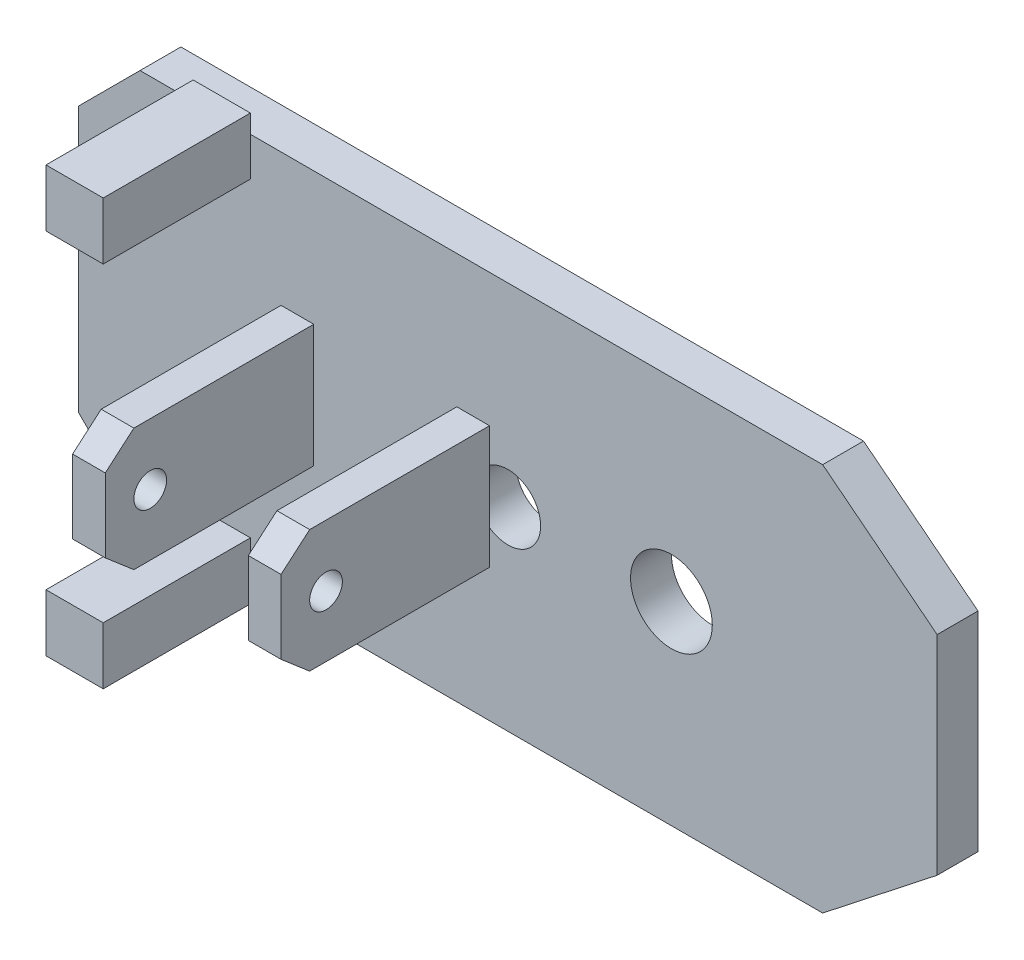
SolidWorks part; units mm, degrees
ref_plane "Front Plane" through (0, 0, 0) normal (0, 0, 1) x (1, 0, 0)
ref_plane "Top Plane" through (0, 0, 0) normal (0, 1, 0) x (1, 0, 0)
ref_plane "Right Plane" through (0, 0, 0) normal (1, 0, 0) x (0, 0, -1)
ref_plane "PL_Sole_Plate_base" through (0, 0, -50) normal (0, 0, 1) x (1, 0, 0)
sketch "SK_Sole_Plate" plane through (0, 0, -50) normal (0, 0, 1) x (1, 0, 0)
  line L0 (-60, -47.5) -> (107, -47.5)
  line L1 (107, -47.5) -> (135, -25.5)
  line L2 (135, -25.5) -> (135, 25.5)
  line L3 (135, 25.5) -> (107, 47.5)
  line L4 (107, 47.5) -> (-60, 47.5)
  line L5 (-60, 47.5) -> (-75, 32.5)
  line L6 (-75, 32.5) -> (-75, -32.5)
  line L7 (-75, -32.5) -> (-60, -47.5)
  circle A0 centre (70, 0) radius 10
  circle A1 centre (30, 0) radius 8
  dimension "D17_SK_Sole_Plate" = 20
  dimension "D19_SK_Sole_Plate" = 16
  dimension "P1" = 60
  dimension "P2" = 47.5
  dimension "P3" = 107
  dimension "P4" = 47.5
  dimension "P5" = 135
  dimension "P6" = 25.5
  dimension "P7" = 135
  dimension "P8" = 25.5
  dimension "P9" = 107
  dimension "P10" = 47.5
  dimension "P11" = 60
  dimension "P12" = 47.5
  dimension "P13" = 75
  dimension "P14" = 32.5
  dimension "P15" = 75
  dimension "P16" = 32.5
  dimension "P18" = 70
  dimension "P20" = 30
extrude "Sole_Plate" add sketch "SK_Sole_Plate" along normal blind 10
ref_plane "PL_Clevis_Front_base" through (17.5, 0, 0) normal (1, 0, 0) x (0, 0, -1)
sketch "SK_Clevis_Front" plane through (17.5, 0, 0) normal (1, 0, 0) x (0, 0, -1)
  line L0 (40, -15) -> (40, 15)
  line L1 (40, 15) -> (-4, 15)
  line L2 (-4, 15) -> (-11, 9)
  line L3 (-11, 9) -> (-11, -9)
  line L4 (-11, -9) -> (-4, -15)
  line L5 (-4, -15) -> (40, -15)
  circle A0 centre (0, 0) radius 4
  dimension "D13_SK_Clevis_Front" = 8
  dimension "P1" = 40
  dimension "P2" = 15
  dimension "P3" = 40
  dimension "P4" = 15
  dimension "P5" = 4
  dimension "P6" = 15
  dimension "P7" = 11
  dimension "P8" = 9
  dimension "P9" = 11
  dimension "P10" = 9
  dimension "P11" = 4
  dimension "P12" = 15
extrude "Clevis_Front" add sketch "SK_Clevis_Front" along normal blind 8
ref_plane "PL_Clevis_Back_base" through (-25.5, 0, 0) normal (1, 0, 0) x (0, 0, -1)
sketch "SK_Clevis_Back" plane through (-25.5, 0, 0) normal (1, 0, 0) x (0, 0, -1)
  line L0 (40, -15) -> (40, 15)
  line L1 (40, 15) -> (-4, 15)
  line L2 (-4, 15) -> (-11, 9)
  line L3 (-11, 9) -> (-11, -9)
  line L4 (-11, -9) -> (-4, -15)
  line L5 (-4, -15) -> (40, -15)
  circle A0 centre (0, 0) radius 4
  dimension "D13_SK_Clevis_Back" = 8
  dimension "P1" = 40
  dimension "P2" = 15
  dimension "P3" = 40
  dimension "P4" = 15
  dimension "P5" = 4
  dimension "P6" = 15
  dimension "P7" = 11
  dimension "P8" = 9
  dimension "P9" = 11
  dimension "P10" = 9
  dimension "P11" = 4
  dimension "P12" = 15
extrude "Clevis_Back" add sketch "SK_Clevis_Back" along normal blind 8
ref_plane "PL_Post_Lat_base" through (0, 0, -40) normal (0, 0, 1) x (1, 0, 0)
sketch "SK_Post_Lat" plane through (0, 0, -40) normal (0, 0, 1) x (1, 0, 0)
  line L0 (-47, 38) -> (-33, 38)
  line L1 (-33, 38) -> (-33, 52)
  line L2 (-33, 52) -> (-47, 52)
  line L3 (-47, 52) -> (-47, 38)
  dimension "P1" = 47
  dimension "P2" = 38
  dimension "P3" = 33
  dimension "P4" = 38
  dimension "P5" = 33
  dimension "P6" = 52
  dimension "P7" = 47
  dimension "P8" = 52
extrude "Post_Lat" add sketch "SK_Post_Lat" along normal blind 36
ref_plane "PL_Post_Med_base" through (0, 0, -40) normal (0, 0, 1) x (1, 0, 0)
sketch "SK_Post_Med" plane through (0, 0, -40) normal (0, 0, 1) x (1, 0, 0)
  line L0 (-47, -52) -> (-33, -52)
  line L1 (-33, -52) -> (-33, -38)
  line L2 (-33, -38) -> (-47, -38)
  line L3 (-47, -38) -> (-47, -52)
  dimension "P1" = 47
  dimension "P2" = 52
  dimension "P3" = 33
  dimension "P4" = 52
  dimension "P5" = 33
  dimension "P6" = 38
  dimension "P7" = 47
  dimension "P8" = 38
extrude "Post_Med" add sketch "SK_Post_Med" along normal blind 36
ref_axis "AX_Roll" through (-85.5, 0, 0) along (1, 0, 0)
sketch "SK_RodBalls" plane through (0, 0, 0) normal (0, 0, 1) x (1, 0, 0)
  point P0 (-40, 45)
  point P2 (-40, -45)
  dimension "P1" = 40
  dimension "P2" = 45
  dimension "P3" = 40
  dimension "P4" = 45
equation "\"Foot_length\" = 210"
equation "\"Foot_width\" = 95"
equation "\"Ankle_height\" = 50"
